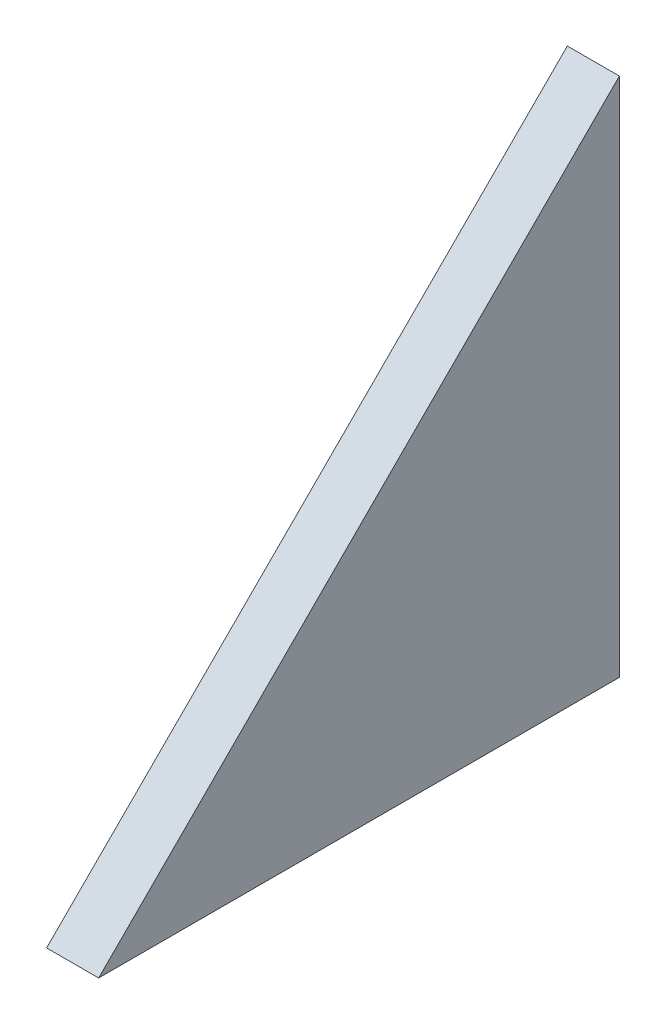
SolidWorks part; units mm, degrees
ref_plane "Front Plane" through (0, 0, 0) normal (0, 0, 1) x (1, 0, 0)
ref_plane "Top Plane" through (0, 0, 0) normal (0, 1, 0) x (1, 0, 0)
ref_plane "Right Plane" through (0, 0, 0) normal (1, 0, 0) x (0, 0, -1)
sketch "Sketch1" plane through (-5.958, 0, 0) normal (1, 0, 0) x (0, 0, -1)
  line L0 (-7.303, -51.9052) -> (-7.303, -21.9052)
  line L1 (-7.303, 48.0948) -> (-7.303, -51.9052) construction
  line L2 (-7.303, -21.9052) -> (-37.303, -51.9052)
  line L3 (-104.303, -51.9052) -> (-4.303, -51.9052) construction
  line L4 (-37.303, -51.9052) -> (-7.303, -51.9052)
  dimension "D1" = 30
  dimension "D2" = 30
sketch "Sketch2" plane through (-5.958, 0, 0) normal (1, 0, 0) x (0, 0, -1)
  line L0 (-7.303, -51.9052) -> (-7.303, -21.9052)
  line L1 (-7.303, 48.0948) -> (-7.303, -51.9052) construction
  line L2 (-7.303, -21.9052) -> (-37.303, -51.9052)
  line L3 (-104.303, -51.9052) -> (-4.303, -51.9052) construction
  line L4 (-37.303, -51.9052) -> (-7.303, -51.9052)
  dimension "D1" = 30
  dimension "D2" = 30
extrude "Boss-Extrude2" add sketch "Sketch2" against normal blind 3
